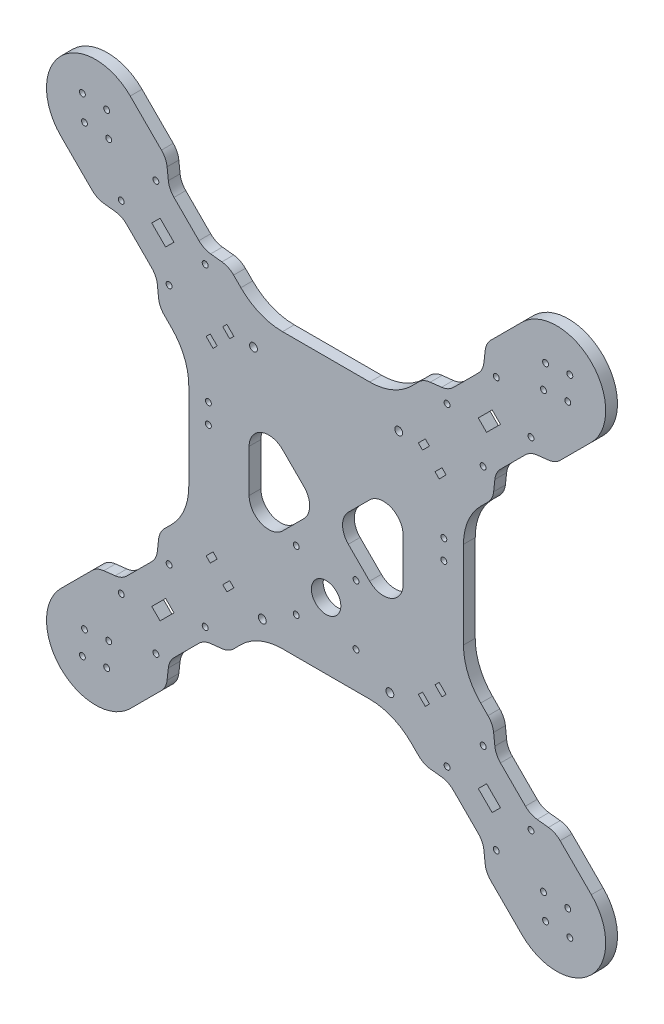
SolidWorks part; units mm, degrees
ref_plane "Front Plane" through (0, 0, 0) normal (0, 0, 1) x (1, 0, 0)
ref_plane "Top Plane" through (0, 0, 0) normal (0, 1, 0) x (1, 0, 0)
ref_plane "Right Plane" through (0, 0, 0) normal (1, 0, 0) x (0, 0, -1)
sketch "Sketch4" plane through (0, 0, 0) normal (0, 0, 1) x (1, 0, 0)
  line L0 (-117.5, 117.5) -> (117.5, -117.5) construction
  line L1 (-117.5, -117.5) -> (117.5, 117.5) construction
  line L2 (-1000, 0) -> (49000, 0) construction
  line L3 (0, -1000) -> (0, 49000) construction
  line L4 (-70, -34.6447) -> (-70, 34.6447)
  line L5 (34.6447, 70) -> (-34.6447, 70)
  line L6 (-70, 34.6447) -> (-135.1777, 99.8223)
  line L7 (-34.6447, 70) -> (-99.8223, 135.1777)
  line L8 (-135.1777, 99.8223) -> (-99.8223, 135.1777) construction
  line L9 (70, -34.6447) -> (70, 34.6447)
  line L10 (70, 34.6447) -> (135.1777, 99.8223)
  line L11 (34.6447, 70) -> (99.8223, 135.1777)
  line L12 (70, -34.6447) -> (135.1777, -99.8223)
  line L13 (34.6447, -70) -> (99.8223, -135.1777)
  line L14 (34.6447, -70) -> (-34.6447, -70)
  line L15 (-34.6447, -70) -> (-99.8223, -135.1777)
  line L16 (-70, -34.6447) -> (-135.1777, -99.8223)
  line L17 (-124.5711, 89.2157) -> (-89.2157, 124.5711) construction
  line L18 (-120.3284, 84.9731) -> (-84.9731, 120.3284) construction
  arc A0 (-135.1777, 99.8223) -> (-99.8223, 135.1777) centre (-117.5, 117.5) cw
  arc A1 (135.1777, 99.8223) -> (99.8223, 135.1777) centre (117.5, 117.5) ccw
  arc A2 (135.1777, -99.8223) -> (99.8223, -135.1777) centre (117.5, -117.5) cw
  arc A3 (-135.1777, -99.8223) -> (-99.8223, -135.1777) centre (-117.5, -117.5) ccw
  point P13 (-117.5, 117.5)
  point P17 (-135.1777, 135.1777)
  point P19 (0, 70)
  point P24 (70, 0)
  point P31 (-70, 0)
  dimension "D6" = 40
  dimension "D1" = 235
  dimension "D2" = 235
  dimension "D3" = 70
  dimension "D4" = 70
  dimension "D5" = 50
  dimension "D7" = 6
extrude "Boss-Extrude1" add sketch "Sketch4" along normal blind 6
fillet "Fillet1" radius 30 8 edges at (34.6447, -70, 3) (70, -34.6447, 3) (70, 34.6447, 3) (34.6447, 70, 3) (-34.6447, 70, 3) (-70, 34.6447, 3) (-70, -34.6447, 3) (-34.6447, -70, 3)
sketch "Sketch8" plane through (0, 0, 6) normal (0, 0, 1) x (1, 0, 0)
  line L0 (-120.3284, 84.9731) -> (-84.9731, 120.3284) construction
  line L1 (-117.5, 117.5) -> (117.5, -117.5) construction
  line L2 (-88.8622, 84.6195) -> (-84.6195, 88.8622)
  line L3 (-88.8622, 84.6195) -> (-81.7911, 77.5485)
  line L4 (-84.6195, 88.8622) -> (-77.5485, 81.7911)
  line L5 (-81.7911, 77.5485) -> (-77.5485, 81.7911)
  circle A0 centre (-104.4185, 86.7409) radius 1.5
  circle A2 centre (-80.0233, 61.6386) radius 1.5
  circle A4 centre (-86.7409, 104.4185) radius 1.5
  circle A5 centre (-61.6386, 80.0233) radius 1.5
  dimension "D1" = 3
  dimension "D2" = 10
  dimension "D3" = 12.5
  dimension "D4" = 13
  dimension "D5" = 45
  dimension "D6" = 10
  dimension "D7" = 12.5
  dimension "D8" = 45
  dimension "D9" = 13
  dimension "D10" = 6
  dimension "D11" = 3
  dimension "D12" = 22.5
  dimension "D13" = 10
sketch "Sketch9" plane through (0, 0, 6) normal (0, 0, 1) x (1, 0, 0)
  line L0 (-135.1777, 99.8223) -> (-99.8223, 135.1777) construction
  line L1 (-117.5, 117.5) -> (117.5, -117.5) construction
  circle A0 centre (-124.2175, 124.2175) radius 1.5
  circle A1 centre (-110.7825, 110.7825) radius 1.5
  circle A2 centre (-123.1569, 111.8431) radius 1.5
  circle A3 centre (-111.8431, 123.1569) radius 1.5
  dimension "D5" = 3
  dimension "D1" = 8
  dimension "D2" = 8
  dimension "D3" = 9.5
  dimension "D4" = 9.5
extrude "Cut-Extrude1" cut sketch "Sketch8" against normal through all both and the other way through all
extrude "Cut-Extrude2" cut sketch "Sketch9" against normal through all both and the other way through all
mirror "Mirror1" about plane through (0, 0, 0) normal (1, 0, 0) of "Cut-Extrude2", "Cut-Extrude1"
mirror "Mirror2" about plane through (0, 0, 0) normal (0, 1, 0) of "Mirror1"
sketch "Sketch10" plane through (0, 0, 6) normal (0, 0, 1) x (1, 0, 0)
  line L0 (-70, -34.6447) -> (-70, 34.6447) construction
  line L1 (70, -34.6447) -> (70, 34.6447) construction
  line L2 (34.6447, 70) -> (-34.6447, 70) construction
  line L3 (-49.1421, -53.3848) -> (-47.0208, -55.5061)
  line L4 (0, -201000) -> (0, 249000) construction
  line L5 (-201000, 0) -> (249000, 0) construction
  line L6 (-4.2426, 0) -> (-39.2426, 35)
  line L7 (-39.2426, 35) -> (-39.2426, -35)
  line L8 (-39.2426, -35) -> (-4.2426, 0)
  line L9 (-117.5, 117.5) -> (117.5, -117.5) construction
  line L10 (-117.5, -117.5) -> (117.5, 117.5) construction
  line L11 (0, -3.3) -> (0, 3.3) construction
  line L12 (39.2426, 35) -> (39.2426, -35)
  line L13 (4.2426, 0) -> (39.2426, 35)
  line L14 (39.2426, -35) -> (4.2426, 0)
  line L21 (3.3, 0) -> (-3.3, 0) construction
  line L22 (-57.6274, -44.8995) -> (-55.5061, -47.0208)
  line L23 (-59.0416, -50.5563) -> (-55.5061, -47.0208)
  line L24 (-61.163, -48.435) -> (-59.0416, -50.5563)
  line L25 (-61.163, 48.435) -> (-59.0416, 50.5563)
  line L26 (-61.163, 48.435) -> (-57.6274, 44.8995)
  line L27 (-57.6274, 44.8995) -> (-55.5061, 47.0208)
  line L28 (-59.0416, 50.5563) -> (-55.5061, 47.0208)
  line L29 (-61.163, -48.435) -> (-57.6274, -44.8995)
  line L30 (57.6274, 44.8995) -> (55.5061, 47.0208)
  line L31 (59.0416, 50.5563) -> (55.5061, 47.0208)
  line L32 (61.163, 48.435) -> (59.0416, 50.5563)
  line L33 (61.163, 48.435) -> (57.6274, 44.8995)
  line L34 (61.163, -48.435) -> (57.6274, -44.8995)
  line L35 (61.163, -48.435) -> (59.0416, -50.5563)
  line L36 (59.0416, -50.5563) -> (55.5061, -47.0208)
  line L37 (57.6274, -44.8995) -> (55.5061, -47.0208)
  line L38 (-52.6777, 56.9203) -> (-50.5563, 59.0416)
  line L39 (-52.6777, 56.9203) -> (-49.1421, 53.3848)
  line L40 (-49.1421, 53.3848) -> (-47.0208, 55.5061)
  line L41 (-50.5563, 59.0416) -> (-47.0208, 55.5061)
  line L42 (-50.5563, -59.0416) -> (-47.0208, -55.5061)
  line L43 (-52.6777, -56.9203) -> (-50.5563, -59.0416)
  line L44 (-52.6777, -56.9203) -> (-49.1421, -53.3848)
  line L45 (52.6777, -56.9203) -> (49.1421, -53.3848)
  line L46 (52.6777, -56.9203) -> (50.5563, -59.0416)
  line L47 (50.5563, -59.0416) -> (47.0208, -55.5061)
  line L48 (49.1421, -53.3848) -> (47.0208, -55.5061)
  line L49 (49.1421, 53.3848) -> (47.0208, 55.5061)
  line L50 (50.5563, 59.0416) -> (47.0208, 55.5061)
  line L51 (52.6777, 56.9203) -> (50.5563, 59.0416)
  line L52 (52.6777, 56.9203) -> (49.1421, 53.3848)
  line L53 (-15.25, -21) -> (15.25, -51.5) construction
  line L54 (-22.2183, -70) -> (22.2183, -70) construction
  circle A0 centre (-60, 20) radius 1.5
  circle A1 centre (-60, 10) radius 1.5
  circle A2 centre (60, 20) radius 1.5
  circle A3 centre (60, 10) radius 1.5
  circle A4 centre (-15.25, -21) radius 1.5
  circle A5 centre (15.25, -21) radius 1.5
  circle A6 centre (-15.25, -51.5) radius 1.5
  circle A7 centre (15.25, -51.5) radius 1.5
  circle A8 centre (0, -36.25) radius 7.5
  circle A9 centre (-37, 55.7426) radius 2
  circle A10 centre (37, 55.7426) radius 2
  circle A11 centre (32.5, -62) radius 2
  circle A12 centre (-32.5, -62) radius 2
  point P87 (0, 0)
  point P88 (0, 0)
  point P90 (26.2827, -62.124)
  dimension "D2" = 10
  dimension "D5" = 3
  dimension "D8" = 3
  dimension "D17" = 15
  dimension "D18" = 4
  dimension "D19" = 4
  dimension "D1" = 10
  dimension "D3" = 10
  dimension "D4" = 50
  dimension "D6" = 30.5
  dimension "D7" = 30.5
  dimension "D9" = 15.25
  dimension "D10" = 21
  dimension "D11" = 3
  dimension "30" = 35
  dimension "D12" = 6
  dimension "D13" = 3
  dimension "D14" = 5
  dimension "D15" = 20
  dimension "D16" = 3
  dimension "D20" = 8
  dimension "D21" = 65
  dimension "D22" = 32.5
extrude "Cut-Extrude3" cut sketch "Sketch10" against normal through all both and the other way through all
fillet "Fillet2" radius 10 6 edges at (4.2426, 0, 3) (39.2426, -35, 3) (39.2426, 35, 3) (-39.2426, -35, 3) (-39.2426, 35, 3) (-4.2426, 0, 3)
sketch "Sketch11" plane through (0, 0, 6) normal (0, 0, 1) x (1, 0, 0)
  line L1 (-34.6447, 70) -> (-99.8223, 135.1777) construction
  line L2 (-80.0233, 104.065) -> (-62.3457, 86.3873)
  line L3 (-62.3457, 86.3873) -> (-49.6177, 84.9731)
  line L4 (-49.6177, 84.9731) -> (-81.4376, 116.7929)
  line L5 (-81.4376, 116.7929) -> (-80.0233, 104.065)
  line L6 (-80.0233, 104.065) -> (-74.3665, 109.7218) construction
  line L7 (-62.3457, 86.3873) -> (-56.6888, 92.0442) construction
  line L8 (-120.3284, 84.9731) -> (-84.9731, 120.3284) construction
  dimension "D1" = 45
  dimension "D2" = 8
  dimension "D3" = 10
  dimension "D4" = 10
  dimension "D5" = 5
extrude "Cut-Extrude4" cut sketch "Sketch11" against normal through all both and the other way through all
ref_plane "Plane1" through (0, 0, 0) normal (0.7071, 0.7071, 0) x (0.7071, -0.7071, 0)
mirror "Mirror4" about plane through (0, 0, 0) normal (0.7071, 0.7071, 0) of "Cut-Extrude4"
ref_axis "Axis1" through (0, 0, 0) along (0, 0, 1)
pattern_circular "CirPattern2" count 4 over 360 about axis through (0, 0, 0) along (0, 0, 1) of "Cut-Extrude4", "Mirror4"
fillet "Fillet3" radius 10 32 edges at (-49.6177, 84.9731, 3) (-62.3457, 86.3873, 3) (-80.0233, 104.065, 3) (-81.4376, 116.7929, 3) (116.7929, 81.4376, 3) (104.065, 80.0233, 3) (86.3873, 62.3457, 3) (84.9731, 49.6177, 3) (80.0233, 104.065, 3) (81.4376, 116.7929, 3) (62.3457, 86.3873, 3) (49.6177, 84.9731, 3) (116.7929, -81.4376, 3) (104.065, -80.0233, 3) (86.3873, -62.3457, 3) (84.9731, -49.6177, 3) (81.4376, -116.7929, 3) (80.0233, -104.065, 3) (62.3457, -86.3873, 3) (49.6177, -84.9731, 3) (-49.6177, -84.9731, 3) (-62.3457, -86.3873, 3) (-80.0233, -104.065, 3) (-81.4376, -116.7929, 3) (-116.7929, -81.4376, 3) (-104.065, -80.0233, 3) (-86.3873, -62.3457, 3) (-84.9731, -49.6177, 3) (-84.9731, 49.6177, 3) (-86.3873, 62.3457, 3) (-104.065, 80.0233, 3) (-116.7929, 81.4376, 3)
sketch "Sketch12" plane through (0, 0, 0) normal (0, 0, 1) x (1, 0, 0)
  line L0 (117.5, 117.5) -> (-117.5, -117.5) construction
  line L1 (-117.5, 117.5) -> (117.5, -117.5) construction
equation "\"D6@Sketch8\"=\"D2@Sketch8\""
equation "\"D7@Sketch8\"=\"D3@Sketch8\""
equation "\"D8@Sketch8\"=\"D5@Sketch8\""
equation "\"D9@Sketch8\"=\"D4@Sketch8\""
equation "\"D2@Sketch9\"=\"D1@Sketch9\""
equation "\"D4@Sketch9\"=\"D3@Sketch9\""
equation "\"D9@Sketch10\"=\"D6@Sketch10\"/2"
equation "\"D22@Sketch10\"= \"D21@Sketch10\" / 2"
